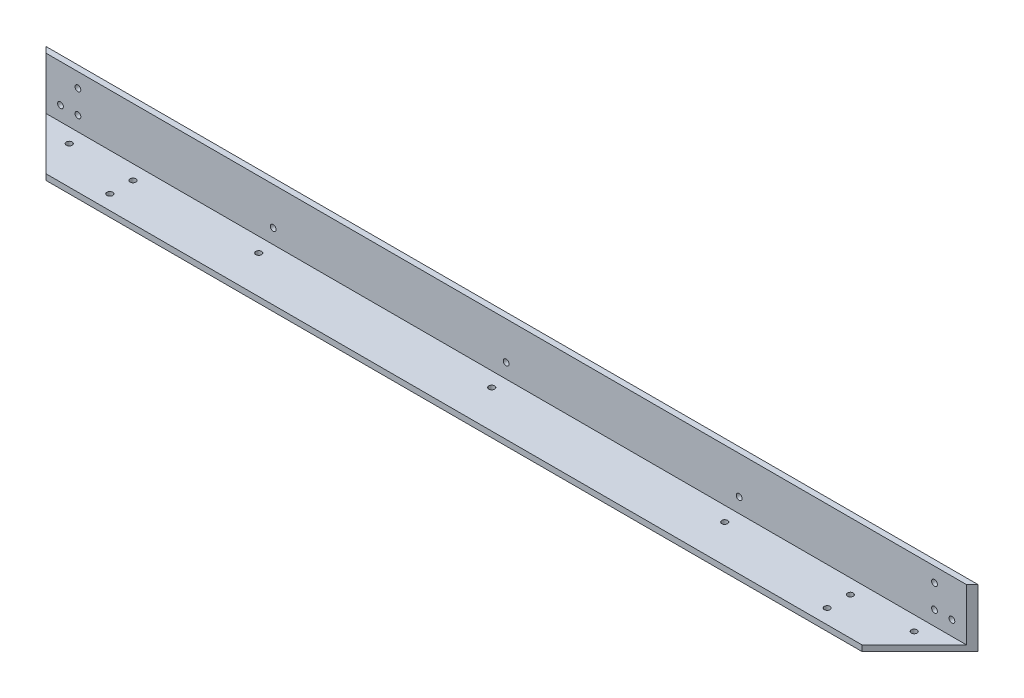
SolidWorks part; units mm, degrees
ref_plane "Front Plane" through (0, 0, 0) normal (0, 0, 1) x (1, 0, 0)
ref_plane "Top Plane" through (0, 0, 0) normal (0, 1, 0) x (1, 0, 0)
ref_plane "Right Plane" through (0, 0, 0) normal (1, 0, 0) x (0, 0, -1)
sketch "Sketch1" plane through (0, 0, 0) normal (1, 0, 0) x (0, 0, -1)
  line L0 (0, 0) -> (-31.75, 0)
  line L1 (-31.75, 0) -> (-31.75, 3.175)
  line L2 (-31.75, 3.175) -> (-3.175, 3.175)
  line L3 (-3.175, 3.175) -> (-3.175, 31.75)
  line L4 (-3.175, 31.75) -> (0, 31.75)
  line L5 (0, 31.75) -> (0, 0)
  dimension "LHeight" = 31.75
  dimension "LWidth" = 31.75
  dimension "LMaterialThickness" = 3.175
  dimension "D1" = 28.575
  dimension "D2" = 28.575
  dimension "D3" = 3.175
extrude "Boss-Extrude1" add sketch "Sketch1" along normal blind 510
chamfer "Chamfer6" distance 31.75 angle 45 1 edges at (510, 1.5875, 31.75)
chamfer "Chamfer7" distance 31.75 angle 45 1 edges at (0, 1.5875, 31.75)
sketch "TopHoles-Sketch3" plane through (0, 3.175, 0) normal (0, 1, 0) x (1, 0, 0)
  line L1 (478.25, -31.75) -> (31.75, -31.75) construction
  line L2 (510, 0) -> (0, 0) construction
  circle A5 centre (58.7375, -23.8125) radius 1.5875
  circle A6 centre (451.2625, -23.8125) radius 1.5875
  circle A9 centre (451.2625, -11.1125) radius 1.5875
  circle A10 centre (58.7375, -11.1125) radius 1.5875
  circle A11 centre (486.1875, -11.1125) radius 1.5875
  circle A12 centre (23.8125, -11.1125) radius 1.5875
  circle A13 centre (127.5, -11.1125) radius 1.5875
  circle A14 centre (255, -11.1125) radius 1.5875
  circle A15 centre (382.5, -11.1125) radius 1.5875
  dimension "D10" = 127.5
  dimension "D9" = 3.175
  dimension "D12" = 7.9375
  dimension "D2" = 11.1125
  dimension "D3" = 23.8125
  dimension "D6" = 23.8125
  dimension "D4" = 34.925
  dimension "D5" = 12.7
  dimension "D7" = 34.925
  dimension "D11" = 127.5
  dimension "D13" = 127.5
extrude "TopHoles-Cut-Extrude2" cut sketch "TopHoles-Sketch3" against normal through all
sketch "FrontHoles-Sketch4" plane through (0, 0, 3.175) normal (0, 0, 1) x (1, 0, 0)
  line L0 (0, 0) -> (0, 31.75) construction
  line L1 (510, 0) -> (510, 31.75) construction
  line L3 (510, 31.75) -> (0, 31.75) construction
  line L7 (510, 0) -> (0, 0) construction
  circle A3 centre (489.3625, 23.8125) radius 1.5875
  circle A4 centre (20.6375, 23.8125) radius 1.5875
  circle A6 centre (11.1125, 11.1125) radius 1.5875
  circle A7 centre (20.6375, 11.1125) radius 1.5875
  circle A8 centre (489.3625, 11.1125) radius 1.5875
  circle A9 centre (498.8875, 11.1125) radius 1.5875
  circle A10 centre (127.5, 11.1125) radius 1.5875
  circle A11 centre (255, 11.1125) radius 1.5875
  circle A12 centre (382.5, 11.1125) radius 1.5875
  dimension "D2" = 3.175
  dimension "D7" = 11.1125
  dimension "D6" = 20.6375
  dimension "D5" = 20.6375
  dimension "D8" = 127.5
  dimension "D9" = 127.5
  dimension "D10" = 127.5
  dimension "D4" = 7.9375
  dimension "D11" = 11.1125
  dimension "D3" = 11.1125
extrude "FrontHoles-Cut-Extrude3" cut sketch "FrontHoles-Sketch4" against normal through all
equation "\"TopRailWidth\"= 1.25in"
equation "\"TopRailHeight\"= 1.25in"
equation "\"RailThickness\"= .125in'Spec"
equation "\"SideRailHoleY1FromEdge\"= \"HoleOffsetFromEdge\""
equation "\"SideRailHoleX1FromSide\"= \"HoleOffsetFromSide\""
equation "\"FrontBackRailLength\"= 510mm"
equation "\"VSWidth\"= 1.25in'Spec"
equation "\"HoleOffsetFromEdge\"= \"RailThickness\" * 2.5"
equation "\"HoleOffsetFromSide\"= \"RailThickness\" * 3.5"
equation "\"TopCBWidth\"= \"TopRailWidth\" - \"RailThickness\"'Equals 28.575"
equation "\"SideRailHoleX2FromSide\"= \"VSWidth\" - \"HoleOffsetFromEdge\" - \"RailThickness\"'Equals 20.6375"
equation "\"FasteningHoleDiameter\"= .125in"
equation "\"SideRailHoleY2FromSide\"= \"HoleOffsetFromSide\""
equation "\"LWidth@Sketch1\"=\"TopRailWidth\""
equation "\"LHeight@Sketch1\"=\"TopRailHeight\""
equation "\"LMaterialThickness@Sketch1\"=\"RailThickness\""
equation "\"D1@Boss-Extrude1\"= \"FrontBackRailLength\""
equation "\"D7@FrontHoles-Sketch4\"=\"SideRailHoleY2FromSide\""
equation "\"D1@Chamfer6\"=\"TopRailWidth\""
equation "\"D1@Chamfer7\"=\"TopRailWidth\""
equation "\"D3@TopHoles-Sketch3\"=\"TopHoleX1FromEdge\" + \"RailThickness\" "
equation "\"D6@TopHoles-Sketch3\"=\"TopHoleX1FromEdge\" + \"RailThickness\""
equation "\"D6@FrontHoles-Sketch4\"=\"SideRailHoleX2FromSide\""
equation "\"TopHoleX1FromEdge\"= \"TopCBWidth\" - \"HoleOffsetFromEdge\"'Equals 20.6375"
equation "\"TopHoleX2FromX1\"= \"TopCBLength\" - \"TopHoleX1FromEdge\" - \"HoleOffsetFromEdge\"'Equals 34.925"
equation "\"TopHoleY1FromSide\"= \"HoleOffsetFromSide\""
equation "\"TopHoleY2FromY1\"= \"TopCBWidth\" - \"TopHoleY1FromEdge\" - \"HoleOffsetFromEdge\"'Equals 12.7"
equation "\"D2@TopHoles-Sketch3\"=\"TopHoleY1FromSide\""
equation "\"D4@TopHoles-Sketch3\"=\"TopHoleX2FromX1\""
equation "\"D5@TopHoles-Sketch3\"=\"TopHoleY2FromY1\""
equation "\"D7@TopHoles-Sketch3\"=\"TopHoleX2FromX1\""
equation "\"TopCBLength\"= \"TopRailWidth\" * 2'Equals 63.5"
equation "\"TopHoleY1FromEdge\"= \"HoleOffsetFromEdge\""
equation "\"FrontOrBackEnclosureOffsets\"= \"FrontBackRailLength\" / 4"
equation "\"D10@TopHoles-Sketch3\"=\"FrontOrBackEnclosureOffsets\""
equation "\"D11@TopHoles-Sketch3\"=\"FrontOrBackEnclosureOffsets\""
equation "\"D13@TopHoles-Sketch3\"=\"FrontOrBackEnclosureOffsets\""
equation "\"D8@FrontHoles-Sketch4\"=\"FrontOrBackEnclosureOffsets\""
equation "\"D9@FrontHoles-Sketch4\"=\"FrontOrBackEnclosureOffsets\""
equation "\"D10@FrontHoles-Sketch4\"=\"FrontOrBackEnclosureOffsets\""
equation "\"D4@FrontHoles-Sketch4\"=\"SideRailHoleY1FromEdge\""
equation "\"D11@FrontHoles-Sketch4\"=\"SideRailHoleX1FromSide\""
equation "\"D2@FrontHoles-Sketch4\"=\"FasteningHoleDiameter\""
equation "\"D3@FrontHoles-Sketch4\"=\"SideRailHoleX1FromSide\""
equation "\"D5@FrontHoles-Sketch4\"=\"SideRailHoleX2FromSide\""
